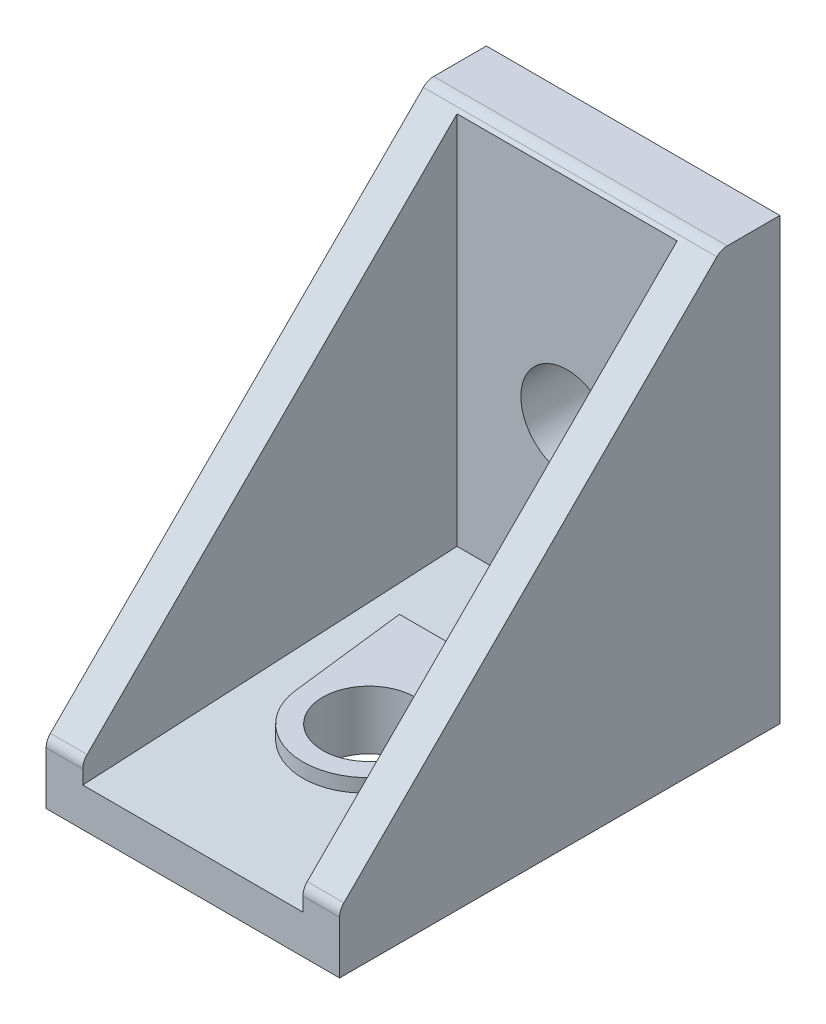
SolidWorks part; units mm, degrees
ref_plane "Front Plane" through (0, 0, 0) normal (0, 0, 1) x (1, 0, 0)
ref_plane "Top Plane" through (0, 0, 0) normal (0, 1, 0) x (1, 0, 0)
ref_plane "Right Plane" through (0, 0, 0) normal (1, 0, 0) x (0, 0, -1)
ref_plane "Plane1" through (0, 0, 0) normal (1, 0, 0) x (0, 0, -1)
sketch "Sketch1" plane through (0, 0, 0) normal (1, 0, 0) x (0, 0, -1)
  line L0 (-30, 0) -> (0, 0)
  line L1 (0, 0) -> (0, 30)
  line L2 (0, 30) -> (-3.5858, 30)
  line L3 (-4.2929, 29.7071) -> (-29.7071, 4.2929)
  line L4 (-30, 3.5858) -> (-30, 0)
  arc A0 (-3.5858, 30) -> (-4.2929, 29.7071) centre (-3.5858, 29) ccw
  arc A1 (-29.7071, 4.2929) -> (-30, 3.5858) centre (-29, 3.5858) ccw
extrude "Boss-Extrude1" add sketch "Sketch1" against normal blind 10 and the other way blind 10
ref_plane "Plane2" through (0, 0, 0) normal (1, 0, 0) x (0, 0, -1)
sketch "Sketch2" plane through (0, 0, 0) normal (1, 0, 0) x (0, 0, -1)
  line L0 (-34, 2.4278) -> (-4.5, 3.9738)
  line L1 (-4.5, 3.9738) -> (-4.5, 34)
  line L2 (-4.5, 34) -> (-34, 34)
  line L3 (-34, 34) -> (-34, 2.4278)
extrude "Cut-Extrude1" cut sketch "Sketch2" against normal blind 7.5 and the other way blind 7.5
ref_plane "Plane3" through (0, 4, 0) normal (0, 1, 0) x (1, 0, 0)
sketch "Sketch3" plane through (0, 4, 0) normal (0, 1, 0) x (1, 0, 0)
  line L0 (-5.4209, -10.5) -> (-4.4687, -18.5299)
  line L1 (4.4687, -18.5299) -> (5.4209, -10.5)
  line L2 (5.4209, -10.5) -> (-5.4209, -10.5)
  arc A0 (-4.4687, -18.5299) -> (4.4687, -18.5299) centre (0, -18) ccw
extrude "Boss-Extrude2" add sketch "Sketch3" against normal blind 2
ref_plane "Plane4" through (0, 0, 0) normal (0, 0, 1) x (1, 0, 0)
sketch "Sketch4" plane through (0, 0, 0) normal (0, 0, 1) x (1, 0, 0)
  circle A0 centre (0, 15) radius 3.15
extrude "Cut-Extrude2" cut sketch "Sketch4" along normal blind 5
ref_plane "Plane5" through (0, 0, 0) normal (0, 1, 0) x (1, 0, 0)
sketch "Sketch5" plane through (0, 0, 0) normal (0, 1, 0) x (1, 0, 0)
  circle A0 centre (0, -18) radius 3.15
extrude "Cut-Extrude3" cut sketch "Sketch5" along normal blind 4
ref_plane "Plane6" through (0, 0, 0) normal (0, 1, 0) x (1, 0, 0)
sketch "Sketch6" plane through (0, 0, 0) normal (0, 1, 0) x (1, 0, 0)
  line L0 (-10, 0) -> (-10, -30)
  line L1 (-10, -30) -> (10, -30)
  line L2 (10, -30) -> (10, 0)
  line L3 (10, 0) -> (-10, 0)
extrude "Boss-Extrude3" add sketch "Sketch6" against normal blind 1
ref_plane "Plane7" through (0, 0, 0) normal (0, 1, 0) x (1, 0, 0)
sketch "Sketch7" plane through (0, 0, 0) normal (0, 1, 0) x (1, 0, 0)
  line L0 (-10, 0) -> (-10, -30)
  line L1 (-10, -30) -> (10, -30)
  line L2 (10, -30) -> (10, 0)
  line L3 (10, 0) -> (-10, 0)
  line L4 (-3.7, -13) -> (3.7, -13)
  line L5 (4, -12.7) -> (4, -5.3)
  line L6 (3.7, -5) -> (-3.7, -5)
  line L7 (-4, -5.3) -> (-4, -12.7)
  line L8 (-3.7, -27) -> (3.7, -27)
  line L9 (4, -26.7) -> (4, -24.3)
  line L10 (3.7, -24) -> (-3.7, -24)
  line L11 (-4, -24.3) -> (-4, -26.7)
  arc A0 (-4, -12.7) -> (-3.7, -13) centre (-3.7, -12.7) ccw
  arc A1 (3.7, -13) -> (4, -12.7) centre (3.7, -12.7) ccw
  arc A2 (4, -5.3) -> (3.7, -5) centre (3.7, -5.3) ccw
  arc A3 (-3.7, -5) -> (-4, -5.3) centre (-3.7, -5.3) ccw
  arc A4 (-4, -26.7) -> (-3.7, -27) centre (-3.7, -26.7) ccw
  arc A5 (3.7, -27) -> (4, -26.7) centre (3.7, -26.7) ccw
  arc A6 (4, -24.3) -> (3.7, -24) centre (3.7, -24.3) ccw
  arc A7 (-3.7, -24) -> (-4, -24.3) centre (-3.7, -24.3) ccw
extrude "Cut-Extrude4" cut sketch "Sketch7" against normal blind 1
ref_plane "Plane8" through (0, 0, 0) normal (0, 0, 1) x (1, 0, 0)
sketch "Sketch8" plane through (0, 0, 0) normal (0, 0, 1) x (1, 0, 0)
  line L0 (-10, 0) -> (10, 0)
  line L1 (10, 0) -> (10, 30)
  line L2 (10, 30) -> (-10, 30)
  line L3 (-10, 30) -> (-10, 0)
extrude "Boss-Extrude4" add sketch "Sketch8" against normal blind 1
ref_plane "Plane9" through (0, 0, 0) normal (0, 0, 1) x (1, 0, 0)
sketch "Sketch9" plane through (0, 0, 0) normal (0, 0, 1) x (1, 0, 0)
  line L0 (-10, 0) -> (10, 0)
  line L1 (10, 0) -> (10, 30)
  line L2 (10, 30) -> (-10, 30)
  line L3 (-10, 30) -> (-10, 0)
  line L4 (0.5, 11) -> (3, 11)
  line L5 (4, 12) -> (4, 14.5)
  line L6 (4, 14.5) -> (3.1101, 14.5)
  line L7 (0.5, 11.8899) -> (0.5, 11)
  line L8 (0.5, 19) -> (0.5, 18.1101)
  line L9 (3.1101, 15.5) -> (4, 15.5)
  line L10 (4, 15.5) -> (4, 18)
  line L11 (3, 19) -> (0.5, 19)
  line L12 (-3, 11) -> (-0.5, 11)
  line L13 (-0.5, 11) -> (-0.5, 11.8899)
  line L14 (-3.1101, 14.5) -> (-4, 14.5)
  line L15 (-4, 14.5) -> (-4, 12)
  line L16 (-4, 15.5) -> (-3.1101, 15.5)
  line L17 (-0.5, 18.1101) -> (-0.5, 19)
  line L18 (-0.5, 19) -> (-3, 19)
  line L19 (-4, 18) -> (-4, 15.5)
  arc A0 (3, 11) -> (4, 12) centre (3, 12) ccw
  arc A1 (3.1101, 14.5) -> (0.5, 11.8899) centre (0, 15) cw
  arc A2 (0.5, 18.1101) -> (3.1101, 15.5) centre (0, 15) cw
  arc A3 (4, 18) -> (3, 19) centre (3, 18) ccw
  arc A4 (-4, 12) -> (-3, 11) centre (-3, 12) ccw
  arc A5 (-0.5, 11.8899) -> (-3.1101, 14.5) centre (0, 15) cw
  arc A6 (-3.1101, 15.5) -> (-0.5, 18.1101) centre (0, 15) cw
  arc A7 (-3, 19) -> (-4, 18) centre (-3, 18) ccw
extrude "Cut-Extrude5" cut sketch "Sketch9" against normal blind 1
